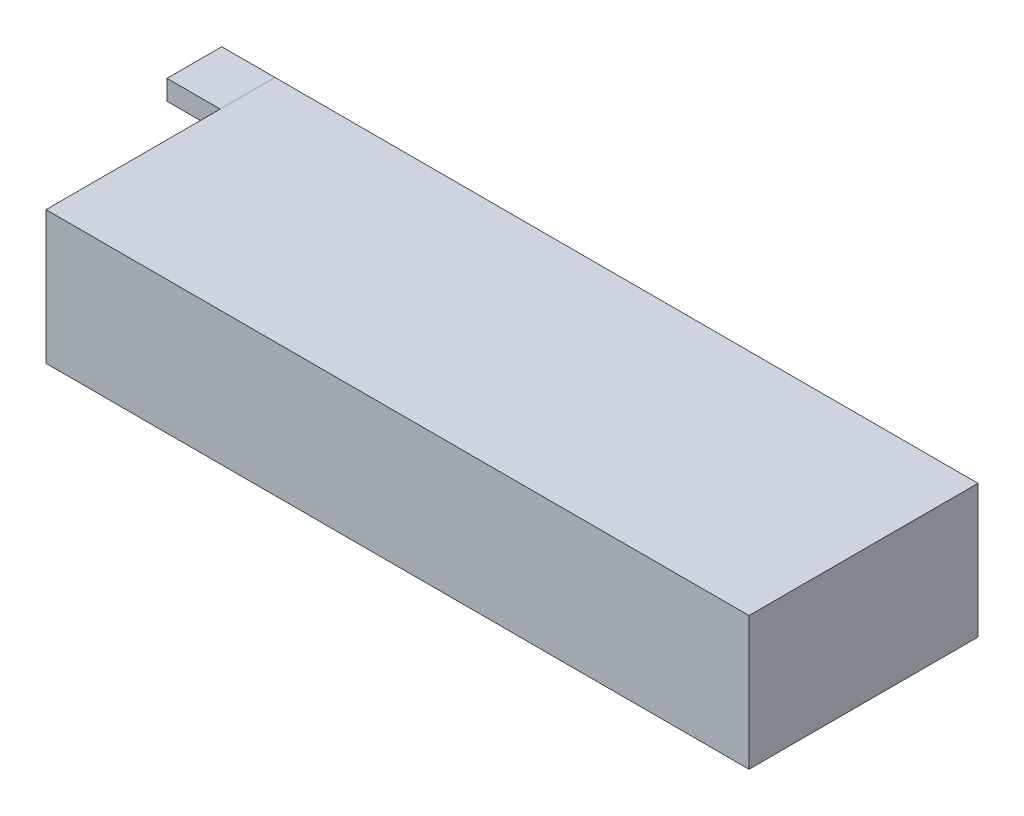
SolidWorks part; units mm, degrees
ref_plane "Front Plane" through (0, 0, 0) normal (0, 0, 1) x (1, 0, 0)
ref_plane "Top Plane" through (0, 0, 0) normal (0, 1, 0) x (1, 0, 0)
ref_plane "Right Plane" through (0, 0, 0) normal (1, 0, 0) x (0, 0, -1)
sketch "Sketch1" plane through (0, 0, 0) normal (0, 1, 0) x (1, 0, 0)
  line L1 (0, 0) -> (132, 0)
  line L2 (0, 0) -> (0, -43)
  line L3 (0, -43) -> (132, -43)
  line L4 (132, 0) -> (132, -43)
  dimension "D1" = 132
  dimension "D2" = 43
extrude "Boss-Extrude1" add sketch "Sketch1" along normal blind 25
sketch "Sketch2" plane through (0, 0, 0) normal (-1, 0, 0) x (0, 0, 1)
  line L0 (0, 25) -> (0, 0) construction
  line L1 (0, 24.9954) -> (10.2798, 24.9954)
  line L2 (0, 24.9954) -> (0, 21.2663)
  line L3 (0, 21.2663) -> (10.2798, 21.2663)
  line L4 (10.2798, 24.9954) -> (10.2798, 21.2663)
  point P6 (10.2798, 21.2663)
extrude "Boss-Extrude2" add sketch "Sketch2" along normal blind 10
